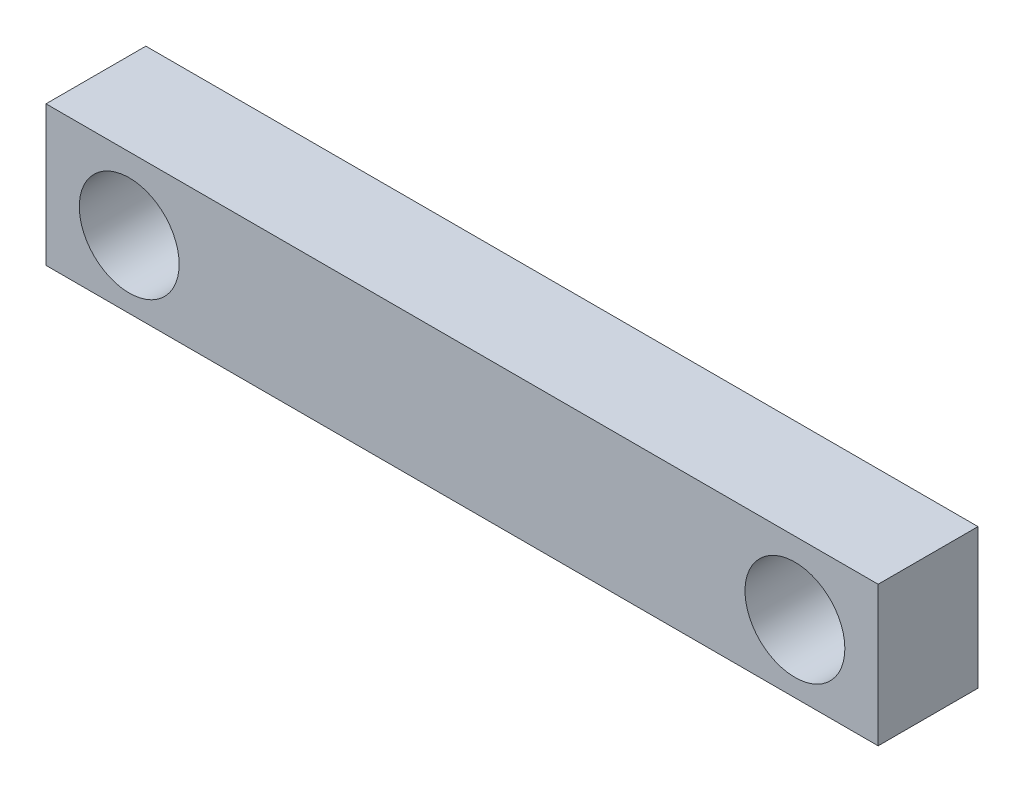
SolidWorks part; units mm, degrees
ref_plane "Front Plane" through (0, 0, 0) normal (0, 0, 1) x (1, 0, 0)
ref_plane "Top Plane" through (0, 0, 0) normal (0, 1, 0) x (1, 0, 0)
ref_plane "Right Plane" through (0, 0, 0) normal (1, 0, 0) x (0, 0, -1)
sketch "Sketch1" plane through (0, 0, 0) normal (0, 0, 1) x (1, 0, 0)
  line L0 (0, 0) -> (1000, 0) construction
  line L6 (-125, 108.7005) -> (1125, 108.7005)
  line L7 (-125, 108.7005) -> (-125, -101.5569)
  line L8 (-125, -101.5569) -> (1125, -101.5569)
  line L9 (1125, 108.7005) -> (1125, -101.5569)
  dimension "D1" = 210.2574
  dimension "D2" = 1250
extrude "Boss-Extrude1" add sketch "Sketch1" along normal blind 150
sketch "Sketch2" plane through (0, 0, 150) normal (0, 0, 1) x (1, 0, 0)
  line L0 (1000, 0) -> (0, 0) construction
  circle A0 centre (0, 0) radius 75
  circle A1 centre (1000, 0) radius 75
  dimension "D1" = 150
  dimension "D3" = 1000
  dimension "D2" = 2
extrude "Cut-Extrude1" cut sketch "Sketch2" against normal blind 150
